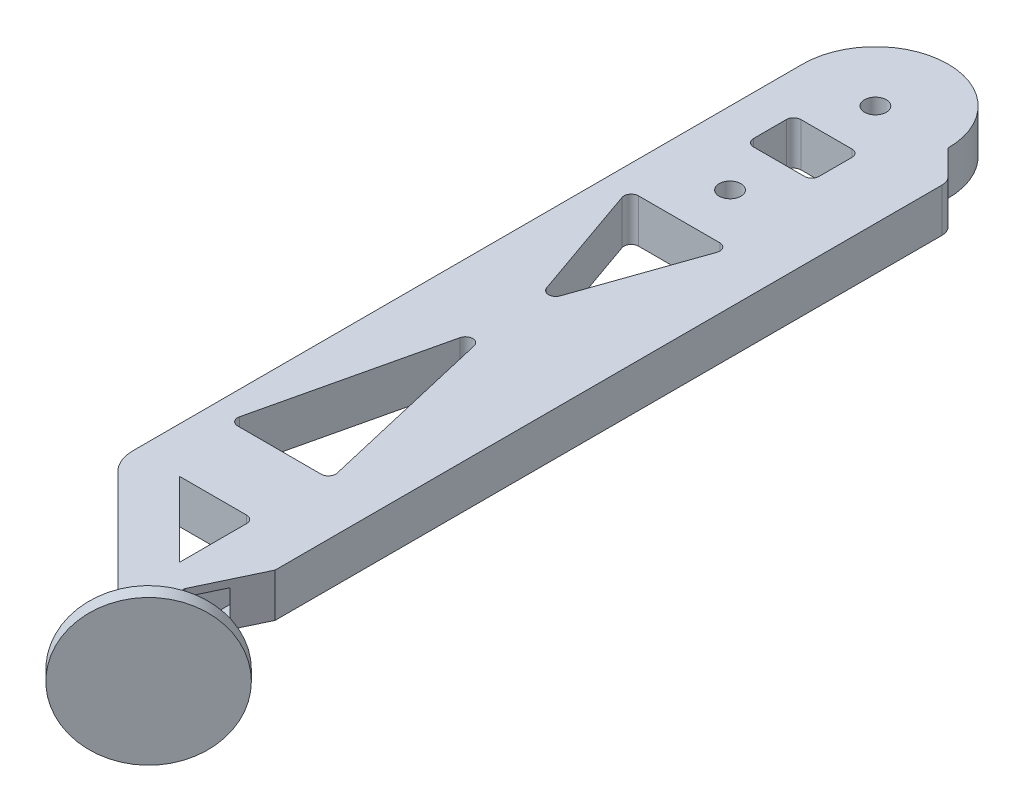
SolidWorks part; units mm, degrees
ref_plane "Front Plane" through (0, 0, 0) normal (0, 0, 1) x (1, 0, 0)
ref_plane "Top Plane" through (0, 0, 0) normal (0, 1, 0) x (1, 0, 0)
ref_plane "Right Plane" through (0, 0, 0) normal (1, 0, 0) x (0, 0, -1)
sketch "Sketch1" plane through (0, 0, 0) normal (0, 1, 0) x (1, 0, 0)
  line L0 (0, 0) -> (0, 20) construction
  line L1 (0, 20) -> (0, 30) construction
  line L2 (0, 0) -> (0, -98) construction
  line L3 (-10, 20) -> (-10, -100)
  line L4 (10, 20) -> (10, -100)
  line L5 (10, -100) -> (-10, -100)
  circle A0 centre (0, 0) radius 1.5
  circle A1 centre (0, 20) radius 1.5
  arc A2 (10, 20) -> (-10, 20) centre (0, 20) ccw
  dimension "D1" = 20
  dimension "D2" = 10
  dimension "D3" = 98
extrude "Boss-Extrude1" add sketch "Sketch1" along normal blind 6 contours A0 | A1 | L4 L5 L3 A2 region at (0, 0, 0) region at (0, 0, -20)
sketch "Sketch3" plane through (0, 6, 0) normal (0, 1, 0) x (1, 0, 0)
  line L0 (0, 0) -> (0, -7) construction
  line L1 (7, -7) -> (-7, -7)
  line L2 (0, -7) -> (0, -27) construction
  line L3 (-7, -7) -> (0, -27)
  line L4 (7, -7) -> (0, -27)
  line L5 (0, -27) -> (0, -32) construction
  line L6 (0, -32) -> (0, -62) construction
  line L7 (7, -62) -> (-7, -62)
  line L8 (-7, -62) -> (0, -32)
  line L9 (7, -62) -> (0, -32)
  line L10 (0, -62) -> (0, -72) construction
  line L11 (0, -72) -> (0, -95) construction
  line L12 (6.5, -95) -> (-6.5, -95) construction
  line L13 (6.5, -72) -> (-6.5, -72)
  line L14 (-6.5, -72) -> (-6.5, -95)
  line L15 (6.5, -72) -> (6.5, -95)
  line L16 (-6.5, -95) -> (6.5, -95)
  line L17 (0, 0) -> (0, 20) construction
  line L19 (-4.5136, 6.7359) -> (4.5136, 6.7359)
  line L20 (-4.5136, 6.7359) -> (-4.5136, 13.2641)
  line L21 (-4.5136, 13.2641) -> (4.5136, 13.2641)
  line L22 (4.5136, 6.7359) -> (4.5136, 13.2641)
  line L23 (-4.5136, 6.7359) -> (4.5136, 13.2641) construction
  line L24 (-4.5136, 13.2641) -> (4.5136, 6.7359) construction
  point P16 (0, 10)
  dimension "D1" = 7
  dimension "D2" = 7
  dimension "D3" = 20
  dimension "D4" = 5
  dimension "D5" = 30
  dimension "D6" = 10
  dimension "D7" = 23
extrude "Cut-Extrude1" cut sketch "Sketch3" against normal blind 14 contours L16 L15 L13 L14 | L7 L8 L9 | L4 L3 L1 | L20 L19 L22 L21
fillet "Fillet1" radius 1 14 edges at (-6.5, 3, 95) (-6.5, 3, 72) (6.5, 3, 72) (6.5, 3, 95) (-7, 3, 62) (7, 3, 62) (0, 3, 32) (-7, 3, 7) (7, 3, 7) (0, 3, 27) (4.5136, 3, -6.7359) (-4.5136, 3, -6.7359) (4.5136, 3, -13.2641) (-4.5136, 3, -13.2641)
sketch "Sketch6" plane through (0, 0, 100) normal (0, 0, 1) x (1, 0, 0)
  line L0 (10, 3) -> (12, 3) construction
  line L1 (10, 6) -> (14, 6)
  line L2 (10, 6) -> (10, 0)
  line L3 (10, 0) -> (14, 0)
  line L4 (14, 6) -> (14, 0)
  line L5 (12, 3) -> (12, 1) construction
  line L6 (10, 1) -> (12, 1)
  line L7 (12, 1) -> (12, 5)
  line L8 (10, 5) -> (12, 5)
  line M10 (10, 0) -> (10, 6)
  dimension "D1" = 4
  dimension "D2" = 2
  dimension "D3" = 2
extrude "Boss-Extrude4" add sketch "Sketch6" against normal blind 120 contours L8 L7 L6 L3 L4 L1 M10 region at (12.5, 3, 100)
sketch "Sketch7" plane through (0, 0, 100) normal (0, 0, 1) x (1, 0, 0)
  line L1 (14, 6) -> (10, 6)
  line L2 (14, 6) -> (14, 0)
  line L3 (14, 0) -> (10, 0)
  line L4 (10, 6) -> (10, 0)
  dimension "D1" = 4
extrude "Cut-Extrude5" cut sketch "Sketch7" against normal blind 15
sketch "Sketch8" plane through (0, 0, 100) normal (0, 0, 1) x (1, 0, 0)
  line L0 (-10, 3) -> (10, 3) construction
  line L1 (-10, 6) -> (-10, 0) construction
  line L2 (10, 6) -> (10, 0) construction
  circle A0 centre (0, 3) radius 10
extrude "Boss-Extrude5" add sketch "Sketch8" along normal blind 2 contours A0
sketch "Sketch9" plane through (0, 6, 0) normal (0, 1, 0) x (1, 0, 0)
  line L0 (10, 20) -> (14, 16)
  line L1 (14, 20) -> (14, -85) construction
  line L2 (14, 16) -> (14, 20)
  line L3 (14, 20) -> (10, 20)
  line L4 (10, -85) -> (14, -76.5825)
  line L5 (14, -76.5825) -> (14, -85)
  line L6 (14, -85) -> (10, -85)
extrude "Cut-Extrude6" cut sketch "Sketch9" against normal blind 18
fillet "Fillet4" radius 2 1 edges at (14, 3, -16)
fillet "Fillet5" radius 5 2 edges at (0, 0, 100) (0, 6, 100)
sketch "Sketch13" plane through (0, 0, 0) normal (0, -1, 0) x (1, 0, 0)
  line L0 (0, 0) -> (0, 80) construction
  line L1 (0, 80) -> (14.1421, 94.1421) construction
  line L2 (0, 80) -> (-15.569, 64.431)
  line L3 (-15.569, 64.431) -> (-15.569, 115.4929)
  line L4 (-15.569, 115.4929) -> (18.2125, 115.4929)
  line L5 (18.2125, 115.4929) -> (14.1421, 94.1421)
  line L6 (14.1421, 94.1421) -> (-15.569, 64.431)
  arc M17 (-6.5, 94) -> (-5.5, 95) centre (-5.5, 94) cw
  line M18 (-5.5, 95) -> (-9.5394, 95)
  line M19 (-9.5394, 95) -> (-9.5394, 100)
  line M20 (-9.5394, 100) -> (-10, 100)
  line M21 (-10, 100) -> (-10, -20)
  line M27 (10, 85) -> (10, 100)
  line M28 (10, 100) -> (9.5394, 100)
  line M29 (9.5394, 100) -> (9.5394, 95)
  line M30 (9.5394, 95) -> (5.5, 95)
  arc M31 (5.5, 95) -> (6.5, 94) centre (5.5, 94) cw
  line M32 (6.5, 94) -> (6.5, 73)
  line M36 (-6.5, 73) -> (-6.5, 94)
  dimension "D1" = 80
  dimension "D2" = 20
extrude "Cut-Extrude8" cut sketch "Sketch13" against normal blind 20 and the other way blind 20 contours L6 L5 L4 L3 L2 M21 M20 M19 M18 M17 M36 M32 M31 M30 M29 M28 M27 region at (-1.7797, 0, 98.0491)
sketch "Sketch14" plane through (0, 0, 0) normal (0, -1, 0) x (1, 0, 0)
  line L0 (0, 0) -> (0, 80) construction
  line L1 (0, 80) -> (19.3607, 99.3607)
  line L2 (0, 80) -> (-16.8572, 63.1428)
  line L3 (-16.8572, 63.1428) -> (-16.8572, 110.2004)
  line L4 (-16.8572, 110.2004) -> (19.3607, 111.5701)
  line L5 (19.3607, 111.5701) -> (19.3607, 99.3607)
  dimension "D1" = 80
extrude "Cut-Extrude9" cut sketch "Sketch14" against normal blind 20 and the other way blind 20
sketch "Sketch15" plane through (0, 0, 0) normal (0, -1, 0) x (1, 0, 0)
  line L0 (0, 0) -> (0, 80) construction
  line L1 (0, 80) -> (14.1421, 94.1421)
  line L2 (14.1421, 94.1421) -> (16.2639, 92.0204)
  line L3 (14.1421, 94.1421) -> (12.0208, 96.2635)
  line L4 (16.2639, 92.0204) -> (10, 85.7565)
  line L5 (10, 85) -> (10, 90) construction
  line L6 (10, 85.7565) -> (-10, 65.7565)
  line L7 (-10, -20) -> (-10, 70) construction
  line L8 (-10, 65.7565) -> (-10, 101.523) construction
  line L9 (12.0208, 96.2635) -> (-10, 74.2426)
  line L10 (-10, 74.2426) -> (-10, 65.7565)
  dimension "D1" = 80
  dimension "D2" = 20
  dimension "D3" = 3
  dimension "D4" = 3.0006
extrude "Boss-Extrude9" add sketch "Sketch15" against normal blind 6 contours L3 L9 L10 L6 L4 L2
sketch "Sketch16" plane through (54.1421, 0, 54.1421) normal (0.7071, 0, 0.7071) x (0.7071, 0, -0.7071)
  line L0 (-59.5685, 6) -> (-53.5679, 0) construction
  circle A0 centre (-56.5682, 3) radius 10
extrude "Boss-Extrude10" add sketch "Sketch16" along normal blind 2 contours A0
fillet "Fillet6" radius 5 1 edges at (-10, 3, 74.2426)
